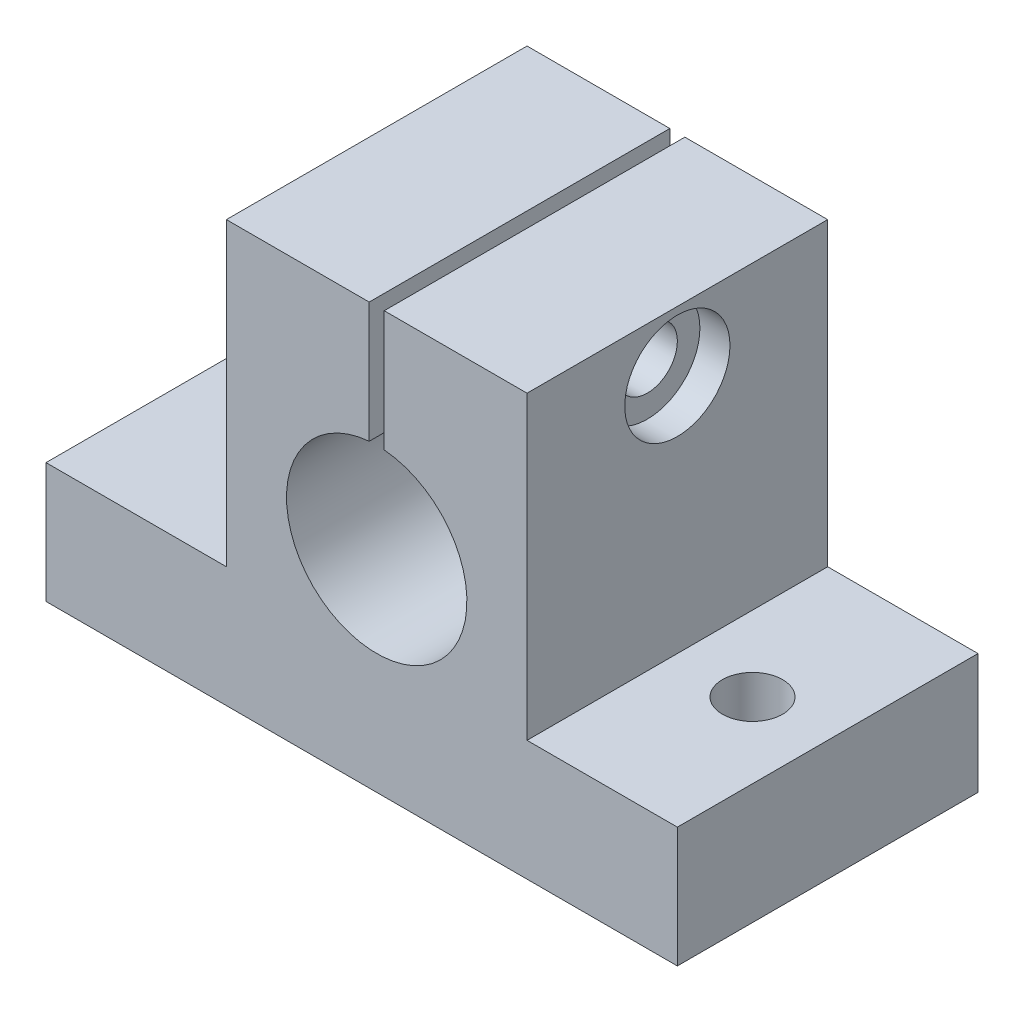
SolidWorks part; units mm, degrees
ref_plane "Спереди" through (0, 0, 0) normal (0, 0, 1) x (1, 0, 0)
ref_plane "Сверху" through (0, 0, 0) normal (0, 1, 0) x (1, 0, 0)
ref_plane "Справа" through (0, 0, 0) normal (1, 0, 0) x (0, 0, -1)
sketch "Эскиз1" plane through (0, 0, 0) normal (0, 0, 1) x (1, 0, 0)
  line L0 (0, 0) -> (0, 14) construction
  line L1 (-22, 0) -> (20, 0)
  line L2 (20, 0) -> (20, 8)
  line L3 (20, 8) -> (10, 8)
  line L4 (10, 8) -> (10, 28)
  line L5 (10, 28) -> (0.5, 28)
  line L6 (0.5, 28) -> (0.5, 19.9791)
  line L7 (-0.5, 19.9791) -> (-0.5, 28)
  line L8 (-0.5, 28) -> (-10, 28)
  line L9 (-10, 28) -> (-10, 8)
  line L10 (-10, 8) -> (-22, 8)
  line L11 (-22, 8) -> (-22, 0)
  arc A0 (-0.5, 19.9791) -> (0.5, 19.9791) centre (0, 14) ccw
  dimension "D1" = 6
  dimension "D2" = 1
  dimension "D3" = 8
  dimension "D4" = 42
  dimension "D5" = 14
  dimension "D6" = 20
  dimension "D7" = 14
  dimension "D8" = 6
extrude "Бобышка-Вытянуть1" add sketch "Эскиз1" along normal blind 20
sketch "Эскиз4" plane through (0, 8, 0) normal (0, 1, 0) x (1, 0, 0)
  line L0 (20, -20) -> (10, -20) construction
  line L1 (-10, -20) -> (-22, -20) construction
  line L2 (20, -20) -> (20, 0) construction
  line L3 (-22, -20) -> (-22, 0) construction
  circle A0 centre (15, -10) radius 2
  circle A1 centre (-17, -10) radius 2
  dimension "D1" = 4
  dimension "D2" = 4
  dimension "D3" = 10
  dimension "D4" = 10
  dimension "D5" = 5
  dimension "D6" = 5
extrude "Вырез-Вытянуть1" cut sketch "Эскиз4" against normal up to surface (8 mm away) up to face at (-1, 0, 10)
sketch "Эскиз5" plane through (10, 0, 0) normal (1, 0, 0) x (0, 0, -1)
  line L0 (-20, 8) -> (-20, 28) construction
  line L1 (-20, 28) -> (0, 28) construction
  circle A0 centre (-10, 24) radius 2
  dimension "D1" = 4
  dimension "D2" = 10
  dimension "D3" = 4
extrude "Вырез-Вытянуть2" cut sketch "Эскиз5" against normal up to surface (20 mm away) up to face at (-10, 18, 10)
sketch "Эскиз6" plane through (10, 0, 0) normal (1, 0, 0) x (0, 0, -1)
  circle A0 centre (-10, 24) radius 3.5
  dimension "D1" = 7
extrude "Вырез-Вытянуть3" cut sketch "Эскиз6" against normal blind 2
sketch "Эскиз7" plane through (-10, 0, 0) normal (-1, 0, 0) x (0, 0, 1)
  line L0 (20, 28) -> (0, 28) construction
  line L1 (14.0415, 24) -> (12.0207, 27.5)
  line L2 (12.0207, 27.5) -> (7.9793, 27.5)
  line L3 (7.9793, 27.5) -> (5.9585, 24)
  line L4 (5.9585, 24) -> (7.9793, 20.5)
  line L5 (7.9793, 20.5) -> (12.0207, 20.5)
  line L6 (12.0207, 20.5) -> (14.0415, 24)
  circle A0 centre (10, 24) radius 3.5 construction
  dimension "D1" = 7
extrude "Вырез-Вытянуть4" cut sketch "Эскиз7" against normal blind 3
